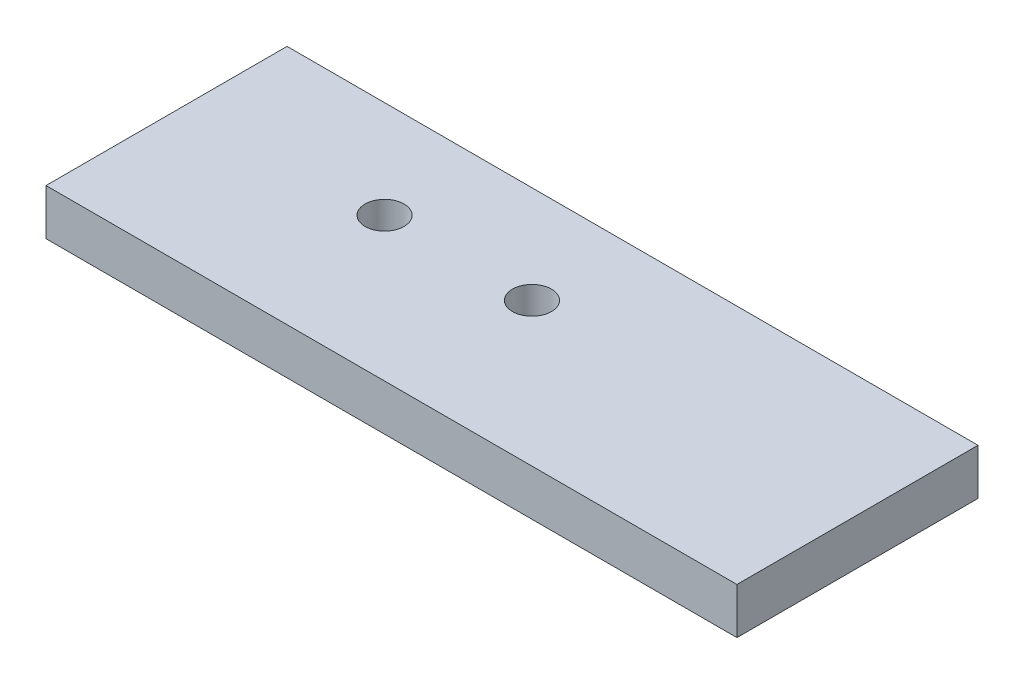
SolidWorks part; units mm, degrees
ref_plane "Front Plane" through (0, 0, 0) normal (0, 0, 1) x (1, 0, 0)
ref_plane "Top Plane" through (0, 0, 0) normal (0, 1, 0) x (1, 0, 0)
ref_plane "Right Plane" through (0, 0, 0) normal (1, 0, 0) x (0, 0, -1)
sketch "Sketch1" plane through (0, 0, 0) normal (0, 1, 0) x (1, 0, 0)
  line L6 (-45, -15.7) -> (45, -15.7)
  line L8 (-45, -15.7) -> (-45, 15.7)
  line L14 (-45, 15.7) -> (45, 15.7)
  line L15 (45, -15.7) -> (45, 15.7)
  line L16 (-45, -15.7) -> (45, 15.7) construction
  line L17 (-45, 15.7) -> (45, -15.7) construction
  point P0 (0, 0)
  dimension "D1" = 31.4
  dimension "D2" = 90
extrude "Boss-Extrude1" add sketch "Sketch1" along normal blind 6
sketch "Sketch2" plane through (0, 6, 0) normal (0, 1, 0) x (1, 0, 0)
  line L0 (-45, 3) -> (-19.6, 3) construction
  line L1 (25, -9.7) -> (-45, -9.7) construction
  line L2 (25, -9.7) -> (25, 15.7) construction
  line L3 (25, 15.7) -> (-45, 15.7) construction
  line L4 (-45, -9.7) -> (-45, 15.7) construction
  line L5 (25, -9.7) -> (-45, 15.7) construction
  line L6 (25, 15.7) -> (-45, -9.7) construction
  line L7 (25, 3) -> (-0.4, 3) construction
  circle A0 centre (-0.4, 3) radius 2.54
  circle A1 centre (-19.6, 3) radius 2.54
  point P0 (-10, 3)
  dimension "D4" = 5.08
  dimension "D1" = 25.4
  dimension "D2" = 70
  dimension "D3" = 25.4
extrude "Cut-Extrude1" cut sketch "Sketch2" against normal through all both and the other way through all
equation "\"testbed_height\" = 91.50mm"
equation "\"plate_thickness\" = 6mm"
equation "\"main_body_splay_length\" = 48.5mm"
equation "\"splay_shaft_length_no_wires\" = 10mm"
equation "\"splay_shaft_length_wires\" = 6.5mm"
equation "\"timing_pulley_offset\" = 0mm"
equation "\"effective_motor_length\" = \"timing_pulley_offset\" + \"splay_shaft_length_no_wires\" + \"main_body_splay_length\""
equation "\"80_20_side\" = 25.4mm"
equation "\"80_20_length\" = 152.4mm"
equation "\"80_20_optic_mount_length\" = \"80_20_length\" - 25.4mm"
equation "\"optic_board_hole_size\" = 6.35mm"
equation "\"total_mounting_length\" = \"testbed_height\" - \"effective_motor_length\" - \"80_20_side\""
equation "\"mounting_vertical_portion_height\" = \"total_mounting_length\" - 2 * \"plate_thickness\""
equation "\"face_mount_width\" = 15.25mm"
equation "\"center_dist_to_face_mount_vertical_screws\" = 5mm"
equation "\"D1@Boss-Extrude1\"=\"plate_thickness\""
